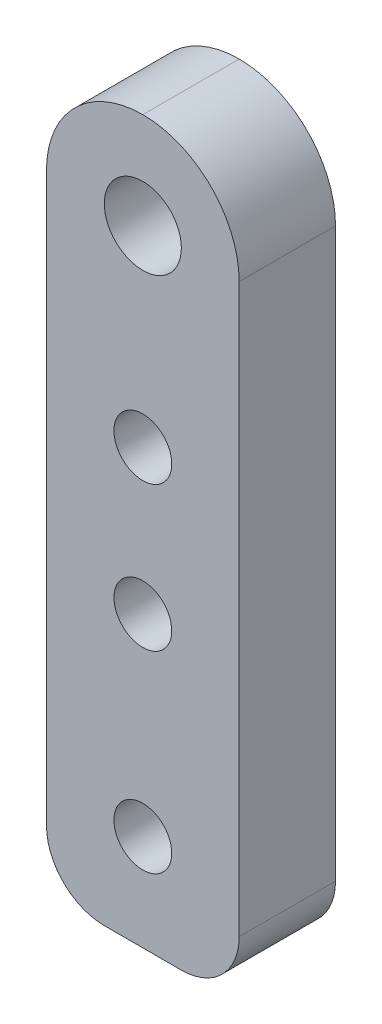
SolidWorks part; units mm, degrees
material "ﾎﾟﾘ塩化ﾋﾞﾆﾙ(PVC)硬質"
ref_plane "正面" through (0, 0, 0) normal (0, 0, 1) x (1, 0, 0)
ref_plane "平面" through (0, 0, 0) normal (0, 1, 0) x (1, 0, 0)
ref_plane "右側面" through (0, 0, 0) normal (1, 0, 0) x (0, 0, -1)
sketch "ｽｹｯﾁ1" plane through (0, 0, 0) normal (0, 0, 1) x (1, 0, 0)
  line L0 (0, 18.725) -> (0, -18.725) construction
  line L1 (-5, -18.725) -> (5, -18.725)
  line L2 (-5, -18.725) -> (-5, 18.725)
  line L3 (-5, 18.725) -> (5, 18.725)
  line L4 (5, -18.725) -> (5, 18.725)
  line L5 (-5, -18.725) -> (5, 18.725) construction
  line L6 (-5, 18.725) -> (5, -18.725) construction
  circle A0 centre (0, -13.725) radius 1.5
  circle A1 centre (0, -3.725) radius 1.5
  circle A2 centre (0, 13.725) radius 2
  circle A3 centre (0, 3.775) radius 1.5
  point P0 (0, 0)
  dimension "D1" = 10
  dimension "D2" = 5
  dimension "D4" = 3
  dimension "D5" = 4
  dimension "D6" = 17.45
  dimension "D7" = 5
  dimension "D8" = 7.5
  dimension "D3" = 10
extrude "ﾎﾞｽ - 押し出し1" add sketch "ｽｹｯﾁ1" along normal blind 5
fillet "ﾌｨﾚｯﾄ1" radius 5 2 edges at (5, 18.725, 2.5) (-5, 18.725, 2.5)
fillet "ﾌｨﾚｯﾄ2" radius 3 2 edges at (-5, -18.725, 2.5) (5, -18.725, 2.5)
